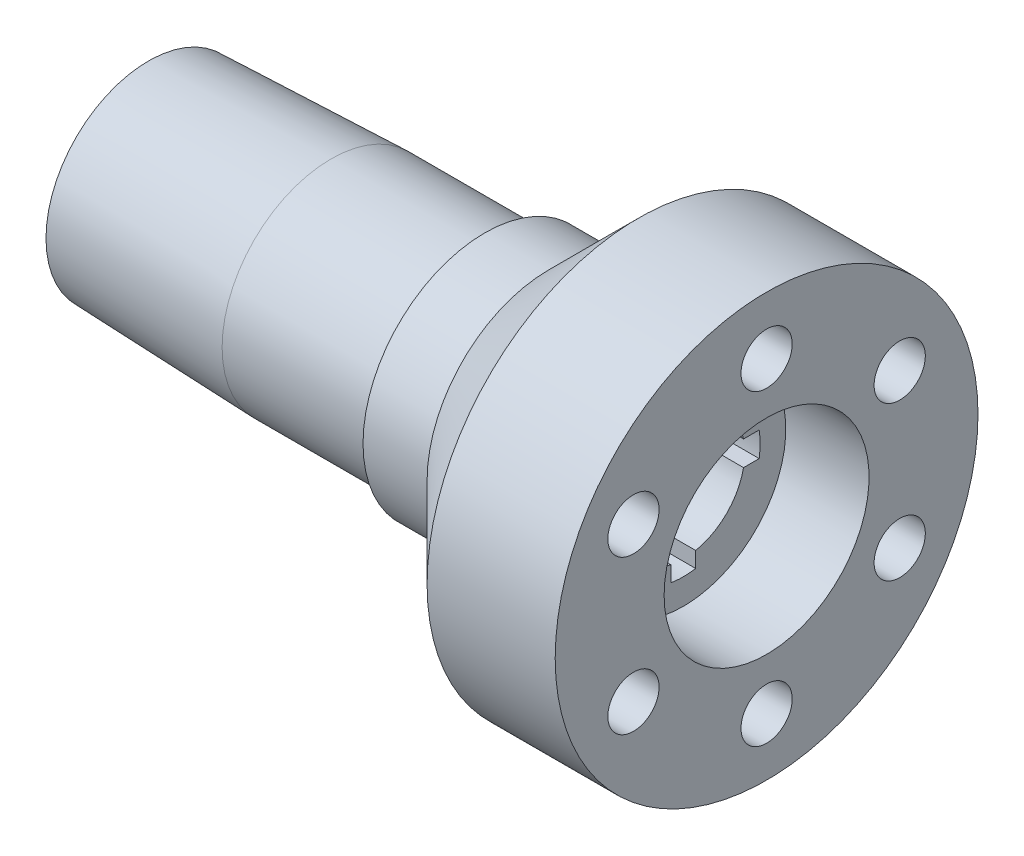
SolidWorks part; units mm, degrees
ref_plane "Front Plane" through (0, 0, 0) normal (0, 0, 1) x (1, 0, 0)
ref_plane "Top Plane" through (0, 0, 0) normal (0, 1, 0) x (1, 0, 0)
ref_plane "Right Plane" through (0, 0, 0) normal (1, 0, 0) x (0, 0, -1)
sketch "Sketch2" plane through (0, 0, 0) normal (0, 0, 1) x (1, 0, 0)
  line L0 (0, 0) -> (64.6823, 0) construction
  line L1 (0, 8) -> (0, 6)
  line L2 (0, 6) -> (41.75, 6)
  line L7 (48.25, 8) -> (48.25, 16.5024)
  line L8 (48.25, 16.5024) -> (38.25, 16.5024)
  line L11 (41.75, 6) -> (41.75, 8)
  line L12 (41.75, 8) -> (48.25, 8)
  line L15 (31.2476, 9.5) -> (38.25, 16.5024)
  line L16 (0, 8) -> (14.2476, 8.5)
  line L17 (14.2476, 8.5) -> (26.2476, 8.5)
  line L19 (26.2476, 8.5) -> (26.2476, 9.5)
  line L20 (26.2476, 9.5) -> (31.2476, 9.5)
  dimension "D1" = 8.5
  dimension "D2" = 6
  dimension "D3" = 8
  dimension "D4" = 6.5
  dimension "D5" = 1
  dimension "D6" = 45
  dimension "D7" = 10
  dimension "D8" = 41.75
  dimension "D9" = 12
  dimension "D10" = 8.5024
  dimension "D11" = 8
  dimension "D12" = 5
revolve "Revolve1" add sketch "Sketch2" angle 360 about L0
sketch "Sketch7" plane through (48.25, 0, 0) normal (1, 0, 0) x (0, 0, -1)
  line L0 (0, -16.5024) -> (0, 16.5024) construction
  circle A0 centre (0, 12) radius 2
  circle A1 centre (0, 0) radius 16.5024 construction
  circle A3 centre (10.3923, 6) radius 2
  circle A4 centre (10.3923, -6) radius 2
  circle A5 centre (0, -12) radius 2
  circle A6 centre (-10.3923, -6) radius 2
  circle A7 centre (-10.3923, 6) radius 2
  point P20 (0, 0)
  dimension "D1" = 4
  dimension "D2" = 12
  dimension "D3" = 6
extrude "Cut-Extrude2" cut sketch "Sketch7" against normal blind 8
sketch "Sketch8" plane through (41.75, 0, 0) normal (1, 0, 0) x (0, 0, -1)
  line L0 (-0.9675, 4.7015) -> (-0.9675, 5.9215)
  line L1 (0.9675, 4.7015) -> (0.9675, 5.9215)
  line L2 (4.7015, 0.9675) -> (5.9215, 0.9675)
  line L3 (4.7015, -0.9675) -> (5.9215, -0.9675)
  line L4 (0.9675, -4.7015) -> (0.9675, -5.9215)
  line L5 (-0.9675, -4.7015) -> (-0.9675, -5.9215)
  line L6 (-4.7015, -0.9675) -> (-5.9215, -0.9675)
  line L7 (-4.7015, 0.9675) -> (-5.9215, 0.9675)
  circle A0 centre (0, 0) radius 4.8
  circle A1 centre (0, 0) radius 6 construction
  point P24 (0, 0)
  circle M4 centre (0, 0) radius 6
  dimension "D1" = 9.6
  dimension "D2" = 1.22
  dimension "D3" = 4
extrude "Boss-Extrude1" add sketch "Sketch8" against normal blind 10 contours A0 L0 L7 M4 | A0 L2 L1 M4 | A0 L4 L3 M4 | A0 L6 L5 M4 region at (41.75, 3.6079, 3.6079) region at (41.75, 3.6079, -3.6079) region at (41.75, -3.6079, 3.6079) region at (41.75, -3.6079, -3.6079)
